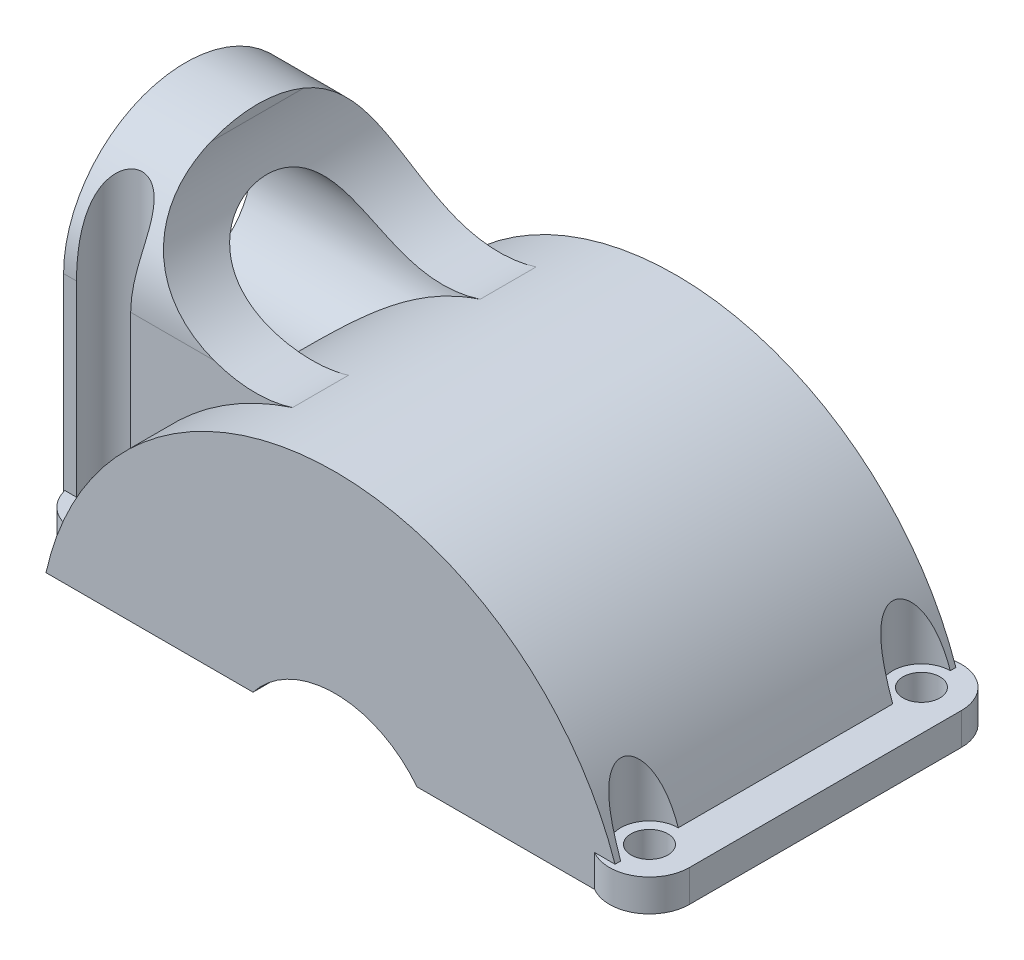
SolidWorks part; units mm, degrees
ref_plane "Front Plane" through (0, 0, 0) normal (0, 0, 1) x (1, 0, 0)
ref_plane "Top Plane" through (0, 0, 0) normal (0, 1, 0) x (1, 0, 0)
ref_plane "Right Plane" through (0, 0, 0) normal (1, 0, 0) x (0, 0, -1)
sketch "Sketch1" plane through (0, 0, 0) normal (0, 1, 0) x (1, 0, 0)
  line L0 (0, 0) -> (-17.5, 0) construction
  line L1 (-17.5, 0) -> (-17.5, -7) construction
  line L2 (0, 0) -> (17.5, 0) construction
  line L3 (17.5, 0) -> (17.5, -8.5) construction
  line L4 (-17.5, 7) -> (-17.5, -7) construction
  line L5 (-15, 7) -> (-15, -7)
  line L6 (-20, 7) -> (-20, -7)
  line L7 (17.5, 8.5) -> (17.5, -8.5) construction
  line L8 (20, 8.5) -> (20, -8.5)
  line L9 (15, 8.5) -> (15, -8.5)
  circle A0 centre (-17.5, -7) radius 1.15
  circle A1 centre (17.5, -8.5) radius 1.15
  circle A2 centre (17.5, 8.5) radius 1.15
  circle A3 centre (-17.5, 7) radius 1.15
  arc A4 (-15, 7) -> (-20, 7) centre (-17.5, 7) ccw
  arc A5 (-20, -7) -> (-15, -7) centre (-17.5, -7) ccw
  arc A6 (20, 8.5) -> (15, 8.5) centre (17.5, 8.5) ccw
  arc A7 (15, -8.5) -> (20, -8.5) centre (17.5, -8.5) ccw
  point P12 (-17.5, 0)
  point P17 (17.5, 0)
  dimension "D4" = 2.3
  dimension "D1" = 35
  dimension "D2" = 7
  dimension "D3" = 8.5
  dimension "D5" = 5
  dimension "D6" = 5
extrude "Boss-Extrude1" add sketch "Sketch1" along normal blind 2
sketch "Sketch2" plane through (0, 0, 0) normal (0, 0, 1) x (1, 0, 0)
  line L0 (0, 0) -> (0, -4) construction
  line L1 (14.975, 0) -> (-14.975, 0) construction
  line L2 (-14.975, 0) -> (-18.0624, 0)
  line L3 (14.975, 0) -> (18.0624, 0)
  arc A0 (14.975, 0) -> (-14.975, 0) centre (0, -4) ccw
  arc A1 (-18.0624, 0) -> (18.0624, 0) centre (0, -4) cw
  point P8 (0, 0)
  point P9 (-25.8877, 0)
  dimension "D2" = 15.5
  dimension "D3" = 3
  dimension "D1" = 4
extrude "Boss-Extrude2" add sketch "Sketch2" along normal blind 8.65 and the other way blind 8.65
sketch "Sketch3" plane through (0, 0, 8.65) normal (0, 0, 1) x (1, 0, 0)
  line L0 (-18.0624, 0) -> (18.0624, 0)
  arc A0 (18.0624, 0) -> (-18.0624, 0) centre (0, -4) ccw construction
  arc A1 (18.0624, 0) -> (-18.0624, 0) centre (0, -4) ccw
extrude "Boss-Extrude3" add sketch "Sketch3" along normal blind 2
mirror "Mirror1" about plane through (0, 0, 0) normal (0, 0, 1) of "Boss-Extrude3"
sketch "Sketch5" plane through (0, 0, -10.65) normal (0, 0, -1) x (-1, 0, 0)
  circle A0 centre (0, -4) radius 6.5
  dimension "D1" = 13
extrude "Cut-Extrude3" cut sketch "Sketch5" against normal through all
ref_plane "Plane1" through (-20, 0, 0) normal (1, 0, 0) x (0, 0, -1)
sketch "Sketch6" plane through (-20, 0, 0) normal (1, 0, 0) x (0, 0, -1)
  line L0 (0, 0) -> (0, 13.7) construction
  line L1 (0, 13.7) -> (0, 0) construction
  line L2 (7.6125, 13.7) -> (7.6125, 0)
  line L3 (-7.6125, 13.7) -> (-7.6125, 0)
  line L4 (7.6125, 0) -> (-7.6125, 0)
  circle A0 centre (0, 13.7) radius 4.1125
  arc A1 (7.6125, 13.7) -> (-7.6125, 13.7) centre (0, 13.7) ccw
  point P4 (0, 6.85)
  dimension "D2" = 8.225
  dimension "D3" = 3.5
  dimension "D1" = 13.7
extrude "Boss-Extrude4" add sketch "Sketch6" along normal blind 4.5
sketch "Sketch4" plane through (0, 2, 0) normal (0, 1, 0) x (1, 0, 0)
  circle A0 centre (17.5, 8.5) radius 1.15 construction
  circle A1 centre (17.5, -8.5) radius 1.15 construction
  circle A3 centre (-17.5, 7) radius 1.15 construction
  circle A4 centre (17.5, -8.5) radius 1.8
  circle A5 centre (17.5, 8.5) radius 1.8
  circle A6 centre (-17.5, -7) radius 1.15 construction
  circle A7 centre (-17.5, 7) radius 1.8
  circle A8 centre (-17.5, -7) radius 1.8
  circle A14 centre (-17.5, -7) radius 1.15 construction
  circle A15 centre (-17.5, 7) radius 1.15 construction
  circle A16 centre (17.5, 8.5) radius 1.15 construction
  circle A17 centre (17.5, -8.5) radius 1.15 construction
  dimension "D1" = 3.6
extrude "Cut-Extrude2" cut sketch "Sketch4" along normal through all
extrude "Cut-Extrude1" cut sketch "Sketch1<2>" along normal through all contours A2 | A1 | A3 | A0 region at (-17.5, 0, 7) region at (17.5, 0, 8.5) region at (17.5, 0, -8.5) region at (-17.5, 0, -7)
sketch "Sketch1<2>" plane through (0, 0, 0) normal (0, 1, 0) x (1, 0, 0) same geometry as "Sketch1"
fillet "Fillet4" radius 7.5 1 edges at (-15.5, 6.0995, 0)
sketch "Sketch7" plane through (0, 0, 0) normal (1, 0, 0) x (0, 0, -1)
  circle A0 centre (0, -4) radius 9
  dimension "D1" = 18
extrude "Cut-Extrude4" cut sketch "Sketch7" against normal up to vertex (14.975 mm away) up to point (-14.975, 0, -8.65)
fillet "Fillet8" radius 7.5 1 edges at (-12.6681, 4.9314, -1.1093)
sketch "Sketch8" plane through (0, 0, 8.65) normal (0, 0, -1) x (-1, 0, 0)
  circle A0 centre (0, -4) radius 7.5
  dimension "D1" = 15
extrude "Cut-Extrude5" cut sketch "Sketch8" against normal blind 1
mirror "Mirror2" about plane through (0, 0, 0) normal (0, 0, 1) of "Cut-Extrude5"
sketch "Sketch10" plane through (-20, 0, 0) normal (-1, 0, 0) x (0, 0, 1)
  circle A0 centre (0, -4) radius 5.5
  point P2 (0, 0)
  dimension "D1" = 11
extrude "Cut-Extrude6" cut sketch "Sketch10" against normal up to surface (5.025 mm away) up to face at (-14.975, 1.9548, 0)
